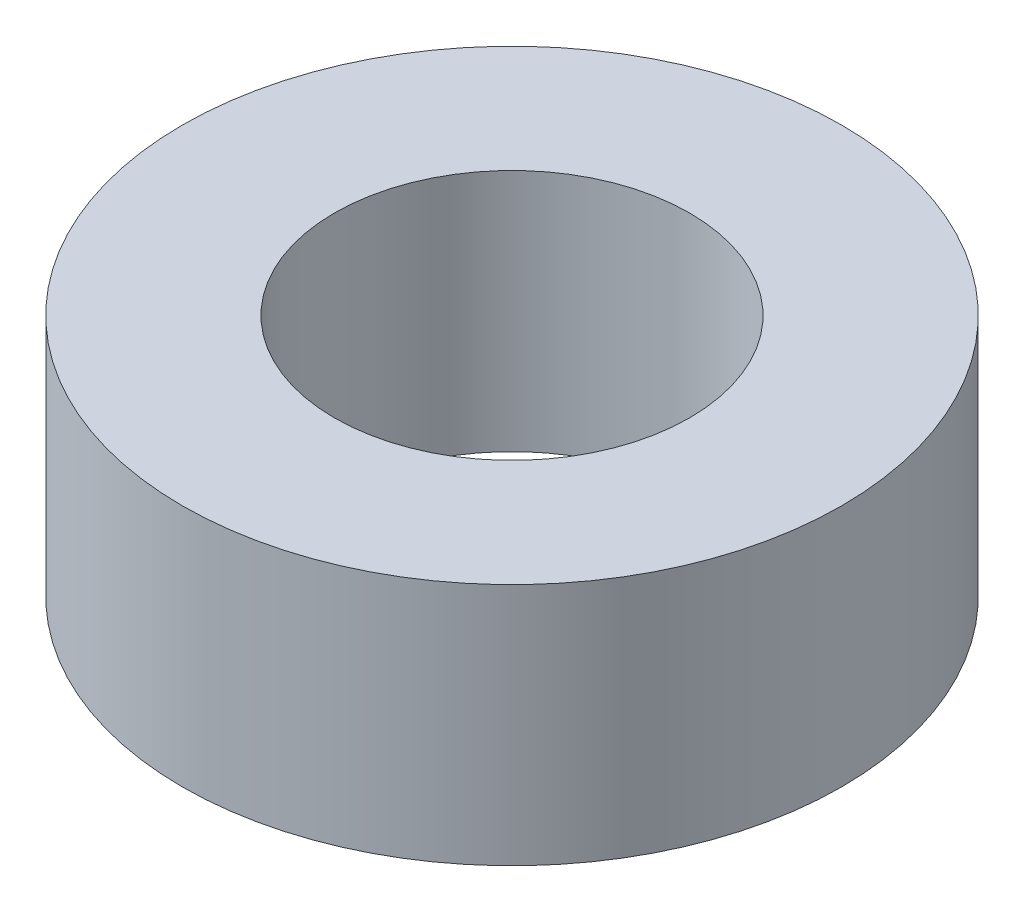
SolidWorks part; units mm, degrees
ref_plane "Front Plane" through (0, 0, 0) normal (0, 0, 1) x (1, 0, 0)
ref_plane "Top Plane" through (0, 0, 0) normal (0, 1, 0) x (1, 0, 0)
ref_plane "Right Plane" through (0, 0, 0) normal (1, 0, 0) x (0, 0, -1)
sketch "Sketch1" plane through (0, 0, 0) normal (0, 1, 0) x (1, 0, 0)
  circle A0 centre (0, 0) radius 32.5
  dimension "FLANGE_OD" = 65
extrude "Boss-Extrude1" add sketch "Sketch1" along normal blind 24
sketch "Sketch2" plane through (0, 0, 0) normal (0, 1, 0) x (1, 0, 0)
  circle A0 centre (0, 0) radius 17.5
  dimension "BORE_D" = 35
extrude "Cut-Extrude1" cut sketch "Sketch2" along normal through all
sketch "Sketch3" plane through (0, 24, 0) normal (0, 1, 0) x (1, 0, 0)
  circle A0 centre (0, 0) radius 14.0245 construction
  circle A1 centre (-14.0245, 0) radius 1.5334
  dimension "BOLT_D" = 3.0669
  dimension "BOLT_PCD" = 28.049
extrude "Cut-Extrude2" cut sketch "Sketch3" against normal blind 21.487 rebuild error yes
pattern_circular "CirPattern1" count 8 over 360 rebuild error yes
